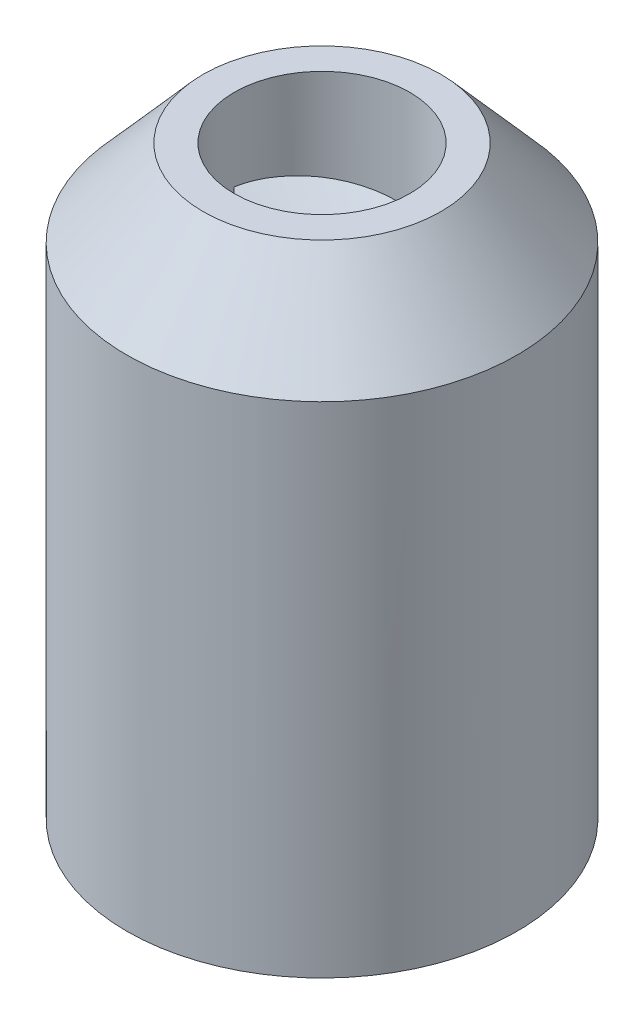
SolidWorks part; units mm, degrees
ref_plane "Front Plane" through (0, 0, 0) normal (0, 0, 1) x (1, 0, 0)
ref_plane "Top Plane" through (0, 0, 0) normal (0, 1, 0) x (1, 0, 0)
ref_plane "Right Plane" through (0, 0, 0) normal (1, 0, 0) x (0, 0, -1)
sketch "Sketch1" plane through (0, 0, 0) normal (0, 1, 0) x (1, 0, 0)
  circle A0 centre (0, 0) radius 2.25
  circle A1 centre (0, 0) radius 5
  dimension "D1" = 4.5
  dimension "D2" = 10
extrude "Base Extrude" add sketch "Sketch1" along normal blind 15
sketch "Sketch3" plane through (0, 0, 0) normal (0, -1, 0) x (1, 0, 0)
  circle A0 centre (0, 0) radius 2.0375
  dimension "D1" = 4.075
curve "Helix/Spiral1" pitch 2 height 12 radius 2.0375 centre (0, 0, 0) axis (0, 1, 0) start towards (0, 0, -1)
sketch "Sketch4" plane through (0, 0, 0) normal (0, 0, 1) x (1, 0, 0)
  line L0 (-2.25, 0.9) -> (-2.25, -0.9)
  line L1 (0, -5.5) -> (0, 5.5) construction
  line L2 (5.5, 0) -> (-5.5, 0) construction
  line L3 (-4.05, 0.2) -> (-2.25, 0.9)
  line L4 (-4.05, 0.2) -> (-4.05, -0.2)
  line L5 (0, 0) -> (-7.0594, 0) construction
  line L7 (-4.05, -0.2) -> (-2.25, -0.9)
  point P6 (-5, 1)
  point P7 (-4.05, 0)
  dimension "D1" = 2.25
  dimension "D2" = 1.8
  dimension "D3" = 1.8
  dimension "D4" = 1
  dimension "D5" = 0.4
sweep "Internal Thread" cut profiles "Sketch4" path "Helix/Spiral1"
sketch "Sketch5" plane through (0, 0, 0) normal (0, 0, 1) x (1, 0, 0)
  line L0 (0, -5.5) -> (0, 5.5) construction
  line L1 (0, 15.8749) -> (5.5204, 15.8749)
  line L2 (0, 15.8749) -> (0, -0.9285)
  line L3 (0, -0.9285) -> (5.5204, -0.9285)
  line L4 (5.5204, 15.8749) -> (5.5204, -0.9285)
extrude "Cutaway View" [suppressed] cut sketch "Sketch5" against normal blind 15
sketch "Sketch6" plane through (0, 0, 0) normal (0, 1, 0) x (1, 0, 0)
  circle A0 centre (0, 0) radius 5
curve "Helix/Spiral2" pitch 0.8 height 15.2 turns 19
sketch "Sketch7" plane through (0, 0, 0) normal (0, 0, 1) x (1, 0, 0)
  line L0 (-5.019, 0.366) -> (-5.019, -0.366)
  line L1 (5.5, 0) -> (-5.5, 0) construction
  line L3 (-4.9983, 0) -> (-5.9147, 0) construction
  line L5 (-4.419, 0.125) -> (-4.419, -0.125)
  line L6 (-4.419, 0.125) -> (-5.019, 0.366)
  line L7 (-4.419, -0.125) -> (-5.019, -0.366)
  point P10 (-4.419, 0)
  dimension "D1" = 0.25
  dimension "D2" = 0.6
sweep "Cable Routing Thread" [suppressed] cut profiles "Sketch7" path "Helix/Spiral2"
ref_axis "Axis1" through (0, 15.9887, 0) along (0, -1, 0)
sketch "Sketch11" plane through (0, 0, 0) normal (0, 0, 1) x (1, 0, 0)
  line L0 (3.4564, 0) -> (3.4564, 8.3026)
  line L2 (3.4564, 0) -> (0, 12.4)
  line L3 (5.5, 0) -> (-5.5, 0) construction
  line L4 (0, 12.4) -> (-1.8459, 12.4)
  line L5 (3.4564, 8.3026) -> (-1.8459, 8.3026)
  line L6 (-1.8459, 12.4) -> (-1.8459, 8.3026)
  spline S1 degree 2 poles (-2.25, 0.9) (-2.25, 1) (-1.8203, 1.1) (-1.3906, 1.2) (-0.6953, 1.3) (0, 1.4) (0.6953, 1.5) (1.3906, 1.6) (1.8203, 1.7) (2.25, 1.8) (2.25, 1.9) (2.25, 2) (1.8203, 2.1) (1.3906, 2.2) (0.6953, 2.3) (0, 2.4) (-0.6953, 2.5) (-1.3906, 2.6) (-1.8203, 2.7) (-2.25, 2.8) (-2.25, 2.9) (-2.25, 3) (-1.8203, 3.1) (-1.3906, 3.2) (-0.6953, 3.3) (0, 3.4) (0.6953, 3.5) (1.3906, 3.6) (1.8203, 3.7) (2.25, 3.8) (2.25, 3.9) (2.25, 4) (1.8203, 4.1) (1.3906, 4.2) (0.6953, 4.3) (0, 4.4) (-0.6953, 4.5) (-1.3906, 4.6) (-1.8203, 4.7) (-2.25, 4.8) (-2.25, 4.9) (-2.25, 5) (-1.8203, 5.1) (-1.3906, 5.2) (-0.6953, 5.3) (0, 5.4) (0.6953, 5.5) (1.3906, 5.6) (1.8203, 5.7) (2.25, 5.8) (2.25, 5.9) (2.25, 6) (1.8203, 6.1) (1.3906, 6.2) (0.6953, 6.3) (0, 6.4) (-0.6953, 6.5) (-1.3906, 6.6) (-1.8203, 6.7) (-2.25, 6.8) (-2.25, 6.9) (-2.25, 7) (-1.8203, 7.1) (-1.3906, 7.2) (-0.6953, 7.3) (0, 7.4) (0.6953, 7.5) (1.3906, 7.6) (1.8203, 7.7) (2.25, 7.8) (2.25, 7.9) (2.25, 8) (1.8203, 8.1) (1.3906, 8.2) (0.6953, 8.3) (0, 8.4) (-0.6953, 8.5) (-1.3906, 8.6) (-1.8203, 8.7) (-2.25, 8.8) (-2.25, 8.9) (-2.25, 9) (-1.8203, 9.1) (-1.3906, 9.2) (-0.6953, 9.3) (0, 9.4) (0.6953, 9.5) (1.3906, 9.6) (1.8203, 9.7) (2.25, 9.8) (2.25, 9.9) (2.25, 10) (1.8203, 10.1) (1.3906, 10.2) (0.6953, 10.3) (0, 10.4) (-0.6953, 10.5) (-1.3906, 10.6) (-1.8203, 10.7) (-2.25, 10.8) (-2.25, 10.9) (-2.25, 11) (-1.8203, 11.1) (-1.3906, 11.2) (-0.6953, 11.3) (0, 11.4) (0.6953, 11.5) (1.3906, 11.6) (1.8203, 11.7) (2.25, 11.8) (2.25, 11.9) (2.25, 12) (1.8203, 12.1) (1.3906, 12.2) (0.6953, 12.3) (0, 12.4) (-0.6953, 12.5) (-1.3906, 12.6) (-1.8203, 12.7) (-2.25, 12.8) (-2.25, 12.9) knots 0 0 0 0.016667 0.016667 0.033333 0.033333 0.05 0.05 0.066667 0.066667 0.083333 0.083333 0.1 0.1 0.116667 0.116667 0.133333 0.133333 0.15 0.15 0.166667 0.166667 0.183333 0.183333 0.2 0.2 0.216667 0.216667 0.233333 0.233333 0.25 0.25 0.266667 0.266667 0.283333 0.283333 0.3 0.3 0.316667 0.316667 0.333333 0.333333 0.35 0.35 0.366667 0.366667 0.383333 0.383333 0.4 0.4 0.416667 0.416667 0.433333 0.433333 0.45 0.45 0.466667 0.466667 0.483333 0.483333 0.5 0.5 0.516667 0.516667 0.533333 0.533333 0.55 0.55 0.566667 0.566667 0.583333 0.583333 0.6 0.6 0.616667 0.616667 0.633333 0.633333 0.65 0.65 0.666667 0.666667 0.683333 0.683333 0.7 0.7 0.716667 0.716667 0.733333 0.733333 0.75 0.75 0.766667 0.766667 0.783333 0.783333 0.8 0.8 0.816667 0.816667 0.833333 0.833333 0.85 0.85 0.866667 0.866667 0.883333 0.883333 0.9 0.9 0.916667 0.916667 0.933333 0.933333 0.95 0.95 0.966667 0.966667 0.983333 0.983333 1 1 1 weights 1 0.951057 1 0.951057 1 0.951057 1 0.951057 1 0.951057 1 0.951057 1 0.951057 1 0.951057 1 0.951057 1 0.951057 1 0.951057 1 0.951057 1 0.951057 1 0.951057 1 0.951057 1 0.951057 1 0.951057 1 0.951057 1 0.951057 1 0.951057 1 0.951057 1 0.951057 1 0.951057 1 0.951057 1 0.951057 1 0.951057 1 0.951057 1 0.951057 1 0.951057 1 0.951057 1 0.951057 1 0.951057 1 0.951057 1 0.951057 1 0.951057 1 0.951057 1 0.951057 1 0.951057 1 0.951057 1 0.951057 1 0.951057 1 0.951057 1 0.951057 1 0.951057 1 0.951057 1 0.951057 1 0.951057 1 0.951057 1 0.951057 1 0.951057 1 0.951057 1 0.951057 1 0.951057 1 0.951057 1 0.951057 1 0.951057 1 0.951057 1 0.951057 1 0.951057 1 0.951057 1 construction
revolve "Thread Chamfer" [suppressed] cut sketch "Sketch11" angle 360 about axis through (0, 15.9887, 0) along (0, -1, 0)
ref_plane "Plane1" through (0, 12.7, 0) normal (0, 1, 0) x (1, 0, 0)
sketch "Sketch12" plane through (0, 12.7, 0) normal (0, 1, 0) x (1, 0, 0)
  circle A0 centre (0, 0) radius 5.08
  dimension "D1" = 10.16
sketch "Sketch13" plane through (0, 15, 0) normal (0, 1, 0) x (1, 0, 0)
  circle A0 centre (0, 0) radius 3.683
  dimension "D1" = 7.366
sketch "Sketch14" plane through (0, 0, 0) normal (1, 0, 0) x (0, 0, -1)
  line L0 (5.08, 12.7) -> (3.048, 15)
  line L1 (5.08, 12.7) -> (-5.08, 12.7) construction
  line L3 (3.048, 15) -> (3.048, 15.5362)
  line L4 (3.048, 15.5362) -> (5.334, 15.5362)
  line L5 (5.334, 15.5362) -> (5.334, 12.7)
  line L6 (5.5, 12.7) -> (-5.5, 12.7) construction
  line L7 (5.334, 12.7) -> (5.08, 12.7)
  dimension "D1" = 2.286
  dimension "D2" = 0.254
sweep "Cut-Sweep1" cut profiles "Sketch14" path "Sketch12"
sketch "Sketch15" [suppressed] plane through (0, 0, 0) normal (1, 0, 0) x (0, 0, -1)
  line L0 (-5, 0) -> (-6.27, 0.7474)
  line L1 (-6.27, 0.7474) -> (-5, 1.4948)
  line L2 (-5, 15) -> (-5, 0) construction
  line L3 (-5, 15) -> (-5, 0) construction
  line L4 (-5, 2.54) -> (-6.27, 3.2874)
  line L5 (-6.27, 3.2874) -> (-5, 4.0348)
  line L6 (-5, 5.08) -> (-6.27, 5.8274)
  line L7 (-6.27, 5.8274) -> (-5, 6.5748)
  line L8 (-5, 7.62) -> (-6.27, 8.3674)
  line L9 (-6.27, 8.3674) -> (-5, 9.1148)
  line L10 (-5, 10.16) -> (-6.27, 10.9074)
  line L11 (-6.27, 10.9074) -> (-5, 11.6548)
  line L12 (-5, 12.7) -> (-6.27, 13.4474)
  line L13 (-6.27, 13.4474) -> (-5, 14.1948)
  line L14 (-5, 0) -> (-5, 1.4948)
  line L15 (-5, 2.54) -> (-5, 4.0348)
  line L16 (-5, 5.08) -> (-5, 6.5748)
  line L17 (-5, 7.62) -> (-5, 9.1148)
  line L18 (-5, 10.16) -> (-5, 11.6548)
  line L19 (-5, 12.7) -> (-5, 14.1948)
  dimension "D1" = 1.27
  dimension "D2" = 6
revolve "Revolve2" [suppressed] add sketch "Sketch15" angle 360 about axis through (0, 15.9887, 0) along (0, -1, 0)
sketch "Sketch16" [suppressed] plane through (0, 15, 0) normal (0, 1, 0) x (1, 0, 0)
  line L0 (-0.635, 4.9595) -> (0, 6.27)
  line L1 (0, 6.27) -> (0.635, 4.9595)
  line L2 (2.4014, 4.3856) -> (3.6854, 5.0725)
  line L3 (3.6854, 5.0725) -> (3.4289, 3.6391)
  line L4 (4.5206, 2.1365) -> (5.9631, 1.9375)
  line L5 (5.9631, 1.9375) -> (4.913, 0.9287)
  line L6 (4.913, -0.9287) -> (5.9631, -1.9375)
  line L7 (5.9631, -1.9375) -> (4.5206, -2.1365)
  line L8 (3.4289, -3.6391) -> (3.6854, -5.0725)
  line L9 (3.6854, -5.0725) -> (2.4014, -4.3856)
  line L10 (0.635, -4.9595) -> (0, -6.27)
  line L11 (0, -6.27) -> (-0.635, -4.9595)
  line L12 (-2.4014, -4.3856) -> (-3.6854, -5.0725)
  line L13 (-3.6854, -5.0725) -> (-3.4289, -3.6391)
  line L14 (-4.5206, -2.1365) -> (-5.9631, -1.9375)
  line L15 (-5.9631, -1.9375) -> (-4.913, -0.9287)
  line L16 (-4.913, 0.9287) -> (-5.9631, 1.9375)
  line L17 (-5.9631, 1.9375) -> (-4.5206, 2.1365)
  line L18 (-3.4289, 3.6391) -> (-3.6854, 5.0725)
  line L19 (-3.6854, 5.0725) -> (-2.4014, 4.3856)
  arc A0 (-0.635, 4.9595) -> (0.635, 4.9595) centre (0, 0) cw
  circle A1 centre (0, 0) radius 5 construction
  circle A2 centre (0, 0) radius 6.27 construction
  arc A3 (2.4014, 4.3856) -> (3.4289, 3.6391) centre (0, 0) cw
  arc A4 (4.5206, 2.1365) -> (4.913, 0.9287) centre (0, 0) cw
  arc A5 (4.913, -0.9287) -> (4.5206, -2.1365) centre (0, 0) cw
  arc A6 (3.4289, -3.6391) -> (2.4014, -4.3856) centre (0, 0) cw
  arc A7 (0.635, -4.9595) -> (-0.635, -4.9595) centre (0, 0) cw
  arc A8 (-2.4014, -4.3856) -> (-3.4289, -3.6391) centre (0, 0) cw
  arc A9 (-4.5206, -2.1365) -> (-4.913, -0.9287) centre (0, 0) cw
  arc A10 (-4.913, 0.9287) -> (-4.5206, 2.1365) centre (0, 0) cw
  arc A11 (-3.4289, 3.6391) -> (-2.4014, 4.3856) centre (0, 0) cw
  point P38 (0, 0)
  circle M1 centre (0, 0) radius 5
  dimension "D1" = 1.27
  dimension "D2" = 10
extrude "Boss-Extrude1" [suppressed] add sketch "Sketch16" against normal up to surface (15 mm away) contours L1 L0 M1 | L3 L2 M1 | L5 L4 M1 | L7 L6 M1 | L9 L8 M1 | L11 L10 M1 | L13 L12 M1 | L15 L14 M1 | L17 L16 M1 | L19 A11 L18
sketch "Sketch17" [suppressed] plane through (0, 0, 0) normal (1, 0, 0) x (0, 0, -1)
  line L0 (-6.27, 13.4474) -> (-4.9345, 14.1948)
  line L1 (-4.9345, 14.1948) -> (-4.9345, 15)
  line L2 (-4.9345, 15) -> (-7.2868, 15)
  line L3 (-7.2868, 15) -> (-7.2868, 13.4474)
  line L4 (-7.2868, 13.4474) -> (-6.27, 13.4474)
  line L5 (-4.9595, 15) -> (-6.27, 15) construction
  line L6 (-4.3856, 15) -> (-4.9595, 15) construction
  line L7 (-4.9595, 14.1948) -> (-4.3856, 14.1948) construction
revolve "Cut-Revolve1" [suppressed] cut sketch "Sketch17" angle 360 about axis through (0, 15.9887, 0) along (0, -1, 0)
